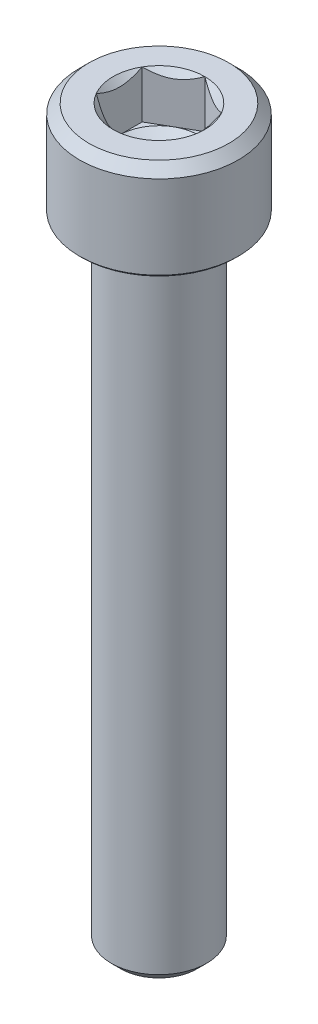
SolidWorks part; units mm, degrees
ref_plane "Front Plane" through (0, 0, 0) normal (0, 0, 1) x (1, 0, 0)
ref_plane "Top Plane" through (0, 0, 0) normal (0, 1, 0) x (1, 0, 0)
ref_plane "Right Plane" through (0, 0, 0) normal (1, 0, 0) x (0, 0, -1)
sketch "Sketch1" plane through (0, 0, 0) normal (0, 0, 1) x (1, 0, 0)
  line L0 (0, 1.5566) -> (2.5, 3)
  line L1 (2.5, 3) -> (2.5, 5.6132)
  line L2 (2.5, 5.6132) -> (2.8868, 6)
  line L3 (2.8868, 6) -> (4.4, 6)
  line L4 (4.4, 6) -> (5, 5.4)
  line L5 (5, 5.4) -> (5, 0.15)
  line L6 (5, 0.15) -> (4.85, 0)
  line L7 (4.85, 0) -> (3.05, 0)
  line L8 (3.05, 0) -> (3, -0.68)
  line L9 (3, -0.68) -> (3, -39.3865)
  line L10 (3, -39.3865) -> (2.3865, -40)
  line L11 (2.3865, -40) -> (0, -40)
  line L12 (0, -40) -> (0, 1.5566)
  line L13 (0, -40) -> (0, 6) construction
revolve "Revolve1" add sketch "Sketch1" angle 360 about L13 reverse direction yes
cosmetic thread "Cosmetic Thread1" parameters "D1"=24, "D2"=4.773
ref_plane "Plane1" through (0, 6, 0) normal (0, 1, 0) x (1, 0, 0)
sketch "Sketch2" plane through (0, 6, 0) normal (0, 1, 0) x (1, 0, 0)
  line L0 (-2.5, -1.4434) -> (0, -2.8868)
  line L1 (0, -2.8868) -> (2.5, -1.4434)
  line L2 (2.5, -1.4434) -> (2.5, 1.4434)
  line L3 (2.5, 1.4434) -> (0, 2.8868)
  line L4 (0, 2.8868) -> (-2.5, 1.4434)
  line L5 (-2.5, 1.4434) -> (-2.5, -1.4434)
extrude "Cut-Extrude1" cut sketch "Sketch2" against normal blind 3
ref_plane "Plane2" through (0, -40, 0) normal (0, 1, 0) x (1, 0, 0)
ref_plane "ANBAU XY" through (0, 0, 0) normal (0, 1, 0) x (1, 0, 0)
ref_plane "ANBAU XZ" through (0, 0, 0) normal (0, 0, 1) x (1, 0, 0)
ref_plane "ANBAU YZ" through (0, 0, 0) normal (1, 0, 0) x (0, 0, -1)
ref_axis "ANBAU X" through (-80.9, 0, 0) along (1, 0, 0)
ref_axis "ANBAU Y" through (0, 0, 50) along (0, 0, -1)
ref_axis "ANBAU Z" through (0, 50, 0) along (0, -1, 0)
sketch3d "ANBAU"
  point P0 (0, 0, 0)
ref_plane "Schraube XY" through (0, 0, 0) normal (0, 1, 0) x (1, 0, 0)
ref_plane "Schraube XZ" through (0, 0, 0) normal (0, 0, 1) x (1, 0, 0)
ref_plane "Schraube YZ" through (0, 0, 0) normal (1, 0, 0) x (0, 0, -1)
ref_axis "Schraube X" through (-80.9, 0, 0) along (1, 0, 0)
ref_axis "Schraube Y" through (0, 0, 50) along (0, 0, -1)
ref_axis "Schraube Z" through (0, 50, 0) along (0, -1, 0)
sketch3d "Schraube"
  point P0 (0, 0, 0)
ref_plane "insert XY" through (0, 0, 0) normal (0, 1, 0) x (1, 0, 0)
ref_plane "insert XZ" through (0, 0, 0) normal (0, 0, 1) x (1, 0, 0)
ref_plane "insert YZ" through (0, 0, 0) normal (1, 0, 0) x (0, 0, -1)
ref_axis "insert X" through (-80.9, 0, 0) along (1, 0, 0)
ref_axis "insert Y" through (0, 0, 50) along (0, 0, -1)
ref_axis "insert Z" through (0, 50, 0) along (0, -1, 0)
sketch3d "insert"
  point P0 (0, 0, 0)
ref_plane "schrauben_punkt XY" through (0, -40, 0) normal (0, 1, 0) x (1, 0, 0)
ref_plane "schrauben_punkt XZ" through (0, 0, 0) normal (0, 0, 1) x (1, 0, 0)
ref_plane "schrauben_punkt YZ" through (0, 0, 0) normal (1, 0, 0) x (0, 0, -1)
ref_axis "schrauben_punkt X" through (-80.9, -40, 0) along (1, 0, 0)
ref_axis "schrauben_punkt Y" through (0, -40, 50) along (0, 0, -1)
ref_axis "schrauben_punkt Z" through (0, 50, 0) along (0, -1, 0)
sketch3d "schrauben_punkt"
  point P0 (0, -40, 0)
other "Freeze***"
